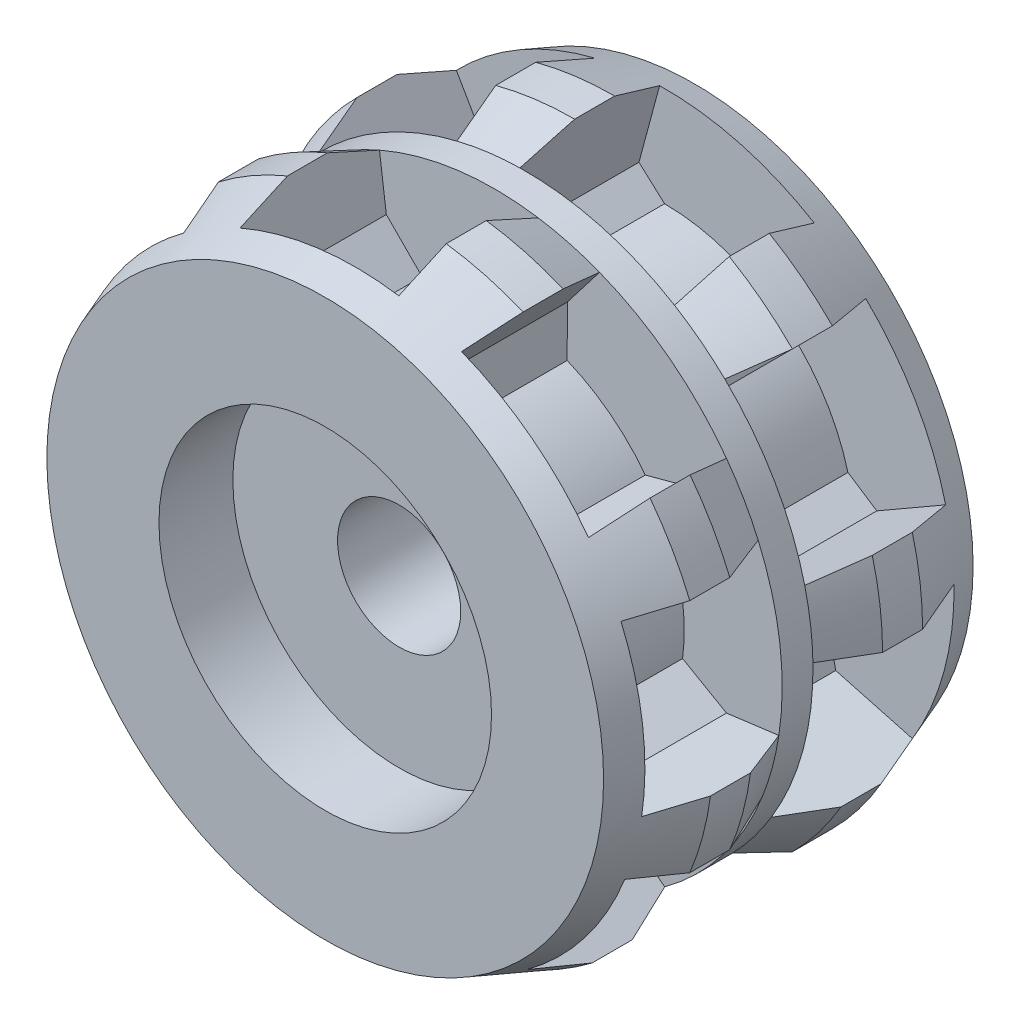
SolidWorks part; units mm, degrees
material "PTFE (general)"
ref_plane "Front Plane" through (0, 0, 0) normal (0, 0, 1) x (1, 0, 0)
ref_plane "Top Plane" through (0, 0, 0) normal (0, 1, 0) x (1, 0, 0)
ref_plane "Right Plane" through (0, 0, 0) normal (1, 0, 0) x (0, 0, -1)
sketch "Sketch1" plane through (0, 0, 0) normal (0, 0, 1) x (1, 0, 0)
  circle A0 centre (-57.4245, 16.5155) radius 23.35
  dimension "D1" = 46.7
extrude "Extrude1" add sketch "Sketch1" along normal blind 2.5
sketch "Sketch2" plane through (0, 0, 2.5) normal (0, 0, 1) x (1, 0, 0)
  circle A0 centre (-57.4245, 16.5155) radius 5
  dimension "D1" = 10
extrude "Extrude2" cut sketch "Sketch2" against normal up to next
sketch "Sketch3" plane through (0, 0, 0) normal (0, 0, -1) x (-1, 0, 0)
  circle A0 centre (57.4245, 16.5155) radius 25
  circle A1 centre (57.4245, 16.5155) radius 5
  dimension "D1" = 10
  dimension "D2" = 50
extrude "Extrude3" add sketch "Sketch3" along normal blind 13.75
sketch "Sketch4" plane through (0, 0, 2.5) normal (0, 0, 1) x (1, 0, 0)
  circle A0 centre (-57.4245, 16.5155) radius 5
  circle A1 centre (-57.4245, 16.5155) radius 25
  dimension "D1" = 50
  dimension "D2" = 10
extrude "Extrude4" add sketch "Sketch4" along normal blind 13.75
chamfer "Chamfer1" distance 1.65 distance2 4 2 edges at (-82.4245, 16.5155, 0) (-32.4245, 16.5155, 2.5) first distance on face at (-82.4245, 16.5155, 0) first distance on face at (-32.4245, 16.5155, 2.5)
chamfer "Chamfer2" distance 6.5 distance2 2.4 2 edges at (-82.4245, 16.5155, -13.75) (-32.4245, 16.5155, 16.25) first distance on face at (-82.4245, 16.5155, -4) first distance on face at (-32.4245, 16.5155, 6.5)
sketch "Sketch5" plane through (0, 0, 0) normal (0, 0, 1) x (1, 0, 0)
  line L0 (-57.4245, 41.5155) -> (-57.4245, 31.9155) construction
  line L1 (-44.8716, 38.1355) -> (-49.692, 29.8334) construction
  line L2 (-57.4245, 41.5155) -> (-59.5045, 33.7906)
  line L3 (-59.5045, 33.7906) -> (-57.4245, 31.9155)
  line L4 (-49.692, 29.8334) -> (-46.9516, 30.4106)
  line L5 (-46.9516, 30.4106) -> (-44.8716, 38.1355)
  line L6 (-46.9516, 30.4106) -> (-59.5045, 33.7906) construction
  line L7 (-53.2281, 32.1006) -> (-57.4245, 16.5155) construction
  line L8 (-50.9245, 40.6557) -> (-53.2281, 32.1006) construction
  line L9 (-39.7469, 34.1932) -> (-46.68, 30.2016)
  line L10 (-40.1937, 18.9354) -> (-33.2606, 22.9269)
  line L11 (-42.5396, 20.4649) -> (-40.1937, 18.9354)
  line L12 (-46.68, 30.2016) -> (-46.5351, 27.4049)
  line L13 (-32.4245, 16.5155) -> (-40.1494, 18.5955)
  line L14 (-43.5294, 6.0426) -> (-35.8045, 3.9626)
  line L15 (-44.1066, 8.7829) -> (-43.5294, 6.0426)
  line L16 (-40.1494, 18.5955) -> (-42.0245, 16.5155)
  line L17 (-39.7469, -1.1622) -> (-43.7384, 5.7709)
  line L18 (-55.0047, -0.7153) -> (-51.0131, -7.6484)
  line L19 (-53.4751, 1.6305) -> (-55.0047, -0.7153)
  line L20 (-43.7384, 5.7709) -> (-46.5351, 5.626)
  line L21 (-57.4245, -8.4845) -> (-55.3445, -0.7596)
  line L22 (-67.8975, 2.6204) -> (-69.9775, -5.1045)
  line L23 (-65.1571, 3.1976) -> (-67.8975, 2.6204)
  line L24 (-55.3445, -0.7596) -> (-57.4245, 1.1155)
  line L25 (-75.1022, -1.1622) -> (-68.1691, 2.8293)
  line L26 (-74.6554, 14.0956) -> (-81.5884, 10.1041)
  line L27 (-72.3095, 12.5661) -> (-74.6554, 14.0956)
  line L28 (-68.1691, 2.8293) -> (-68.314, 5.626)
  line L29 (-82.4245, 16.5155) -> (-74.6997, 14.4355)
  line L30 (-71.3197, 26.9884) -> (-79.0445, 29.0684)
  line L31 (-70.7425, 24.2481) -> (-71.3197, 26.9884)
  line L32 (-74.6997, 14.4355) -> (-72.8245, 16.5155)
  line L33 (-75.1022, 34.1932) -> (-71.1107, 27.2601)
  line L34 (-59.8444, 33.7463) -> (-63.8359, 40.6794)
  line L35 (-61.374, 31.4004) -> (-59.8444, 33.7463)
  line L36 (-71.1107, 27.2601) -> (-68.314, 27.4049)
  arc A0 (-57.4245, 41.5155) -> (-44.8716, 38.1355) centre (-57.4245, 16.5155) cw
  circle A1 centre (-57.4245, 16.5155) radius 25 construction
  arc A2 (-57.4245, 31.9155) -> (-49.692, 29.8334) centre (-57.4245, 16.5155) cw
  arc A3 (-39.7469, 34.1932) -> (-33.2606, 22.9269) centre (-57.4245, 16.5155) cw
  arc A4 (-46.5351, 27.4049) -> (-42.5396, 20.4649) centre (-57.4245, 16.5155) cw
  arc A5 (-32.4245, 16.5155) -> (-35.8045, 3.9626) centre (-57.4245, 16.5155) cw
  arc A6 (-42.0245, 16.5155) -> (-44.1066, 8.7829) centre (-57.4245, 16.5155) cw
  arc A7 (-39.7469, -1.1622) -> (-51.0131, -7.6484) centre (-57.4245, 16.5155) cw
  arc A8 (-46.5351, 5.626) -> (-53.4751, 1.6305) centre (-57.4245, 16.5155) cw
  arc A9 (-57.4245, -8.4845) -> (-69.9775, -5.1045) centre (-57.4245, 16.5155) cw
  arc A10 (-57.4245, 1.1155) -> (-65.1571, 3.1976) centre (-57.4245, 16.5155) cw
  arc A11 (-75.1022, -1.1622) -> (-81.5884, 10.1041) centre (-57.4245, 16.5155) cw
  arc A12 (-68.314, 5.626) -> (-72.3095, 12.5661) centre (-57.4245, 16.5155) cw
  arc A13 (-82.4245, 16.5155) -> (-79.0445, 29.0684) centre (-57.4245, 16.5155) cw
  arc A14 (-72.8245, 16.5155) -> (-70.7425, 24.2481) centre (-57.4245, 16.5155) cw
  arc A15 (-75.1022, 34.1932) -> (-63.8359, 40.6794) centre (-57.4245, 16.5155) cw
  arc A16 (-68.314, 27.4049) -> (-61.374, 31.4004) centre (-57.4245, 16.5155) cw
  dimension "D1" = 13
  dimension "D2" = 9.6
  dimension "D3" = 8
extrude "Extrude5" cut sketch "Sketch5" against normal blind 11.3
ref_plane "Plane1" through (0, 0, 2.5) normal (0, 0, 1) x (1, 0, 0)
sketch "Sketch7" plane through (0, 0, 2.5) normal (0, 0, 1) x (1, 0, 0)
  line L0 (-47.8575, 39.6125) -> (-51.5312, 30.7432) construction
  line L1 (-37.5536, 31.686) -> (-45.184, 25.8605) construction
  line L2 (-57.4245, 16.5155) -> (-47.8575, 39.6125) construction
  line L3 (-57.4245, 16.5155) -> (-57.4245, 41.5155) construction
  line L4 (-47.8575, 39.6125) -> (-51.5158, 34.8568)
  line L5 (-51.5158, 34.8568) -> (-51.5312, 30.7432)
  line L6 (-45.184, 25.8605) -> (-41.2119, 26.9303)
  line L7 (-41.2119, 26.9303) -> (-37.5536, 31.686)
  line L8 (-51.5158, 34.8568) -> (-41.2119, 26.9303) construction
  line L9 (-46.3639, 30.8936) -> (-42.1813, 36.3307) construction
  line L10 (-46.3639, 30.8936) -> (-57.4245, 16.5155) construction
  line L11 (-34.3276, 26.0826) -> (-40.2772, 25.3067)
  line L12 (-40.2772, 25.3067) -> (-43.1968, 22.4088)
  line L13 (-42.1613, 14.4681) -> (-38.5961, 12.4158)
  line L14 (-38.5961, 12.4158) -> (-32.6465, 13.1917)
  line L15 (-34.3276, 6.9484) -> (-39.0832, 10.6068)
  line L16 (-39.0832, 10.6068) -> (-43.1968, 10.6222)
  line L17 (-48.0795, 4.275) -> (-47.0097, 0.3029)
  line L18 (-47.0097, 0.3029) -> (-42.2541, -3.3555)
  line L19 (-47.8575, -6.5815) -> (-48.6333, -0.6319)
  line L20 (-48.6333, -0.6319) -> (-51.5312, 2.2877)
  line L21 (-59.472, 1.2522) -> (-61.5242, -2.313)
  line L22 (-61.5242, -2.313) -> (-60.7483, -8.2626)
  line L23 (-66.9916, -6.5815) -> (-63.3332, -1.8258)
  line L24 (-63.3332, -1.8258) -> (-63.3179, 2.2877)
  line L25 (-69.6651, 7.1705) -> (-73.6372, 6.1007)
  line L26 (-73.6372, 6.1007) -> (-77.2955, 1.345)
  line L27 (-80.5215, 6.9484) -> (-74.5719, 7.7243)
  line L28 (-74.5719, 7.7243) -> (-71.6523, 10.6222)
  line L29 (-72.6878, 18.5629) -> (-76.253, 20.6151)
  line L30 (-76.253, 20.6151) -> (-82.2026, 19.8393)
  line L31 (-80.5215, 26.0826) -> (-75.7659, 22.4242)
  line L32 (-75.7659, 22.4242) -> (-71.6523, 22.4088)
  line L33 (-66.7696, 28.756) -> (-67.8394, 32.7281)
  line L34 (-67.8394, 32.7281) -> (-72.595, 36.3865)
  line L35 (-66.9916, 39.6125) -> (-66.2157, 33.6629)
  line L36 (-66.2157, 33.6629) -> (-63.3179, 30.7432)
  line L37 (-55.3771, 31.7788) -> (-53.3249, 35.3439)
  line L38 (-53.3249, 35.3439) -> (-54.1008, 41.2936)
  arc A0 (-47.8575, 39.6125) -> (-37.5536, 31.686) centre (-57.4245, 16.5155) cw
  arc A1 (-51.5312, 30.7432) -> (-45.184, 25.8605) centre (-57.4245, 16.5155) cw
  circle A3 centre (-57.4245, 16.5155) radius 25 construction
  arc A4 (-34.3276, 26.0826) -> (-32.6465, 13.1917) centre (-57.4245, 16.5155) cw
  arc A5 (-43.1968, 22.4088) -> (-42.1613, 14.4681) centre (-57.4245, 16.5155) cw
  arc A6 (-34.3276, 6.9484) -> (-42.2541, -3.3555) centre (-57.4245, 16.5155) cw
  arc A7 (-43.1968, 10.6222) -> (-48.0795, 4.275) centre (-57.4245, 16.5155) cw
  arc A8 (-47.8575, -6.5815) -> (-60.7483, -8.2626) centre (-57.4245, 16.5155) cw
  arc A9 (-51.5312, 2.2877) -> (-59.472, 1.2522) centre (-57.4245, 16.5155) cw
  arc A10 (-66.9916, -6.5815) -> (-77.2955, 1.345) centre (-57.4245, 16.5155) cw
  arc A11 (-63.3179, 2.2877) -> (-69.6651, 7.1705) centre (-57.4245, 16.5155) cw
  arc A12 (-80.5215, 6.9484) -> (-82.2026, 19.8393) centre (-57.4245, 16.5155) cw
  arc A13 (-71.6523, 10.6222) -> (-72.6878, 18.5629) centre (-57.4245, 16.5155) cw
  arc A14 (-80.5215, 26.0826) -> (-72.595, 36.3865) centre (-57.4245, 16.5155) cw
  arc A15 (-71.6523, 22.4088) -> (-66.7696, 28.756) centre (-57.4245, 16.5155) cw
  arc A16 (-66.9916, 39.6125) -> (-54.1008, 41.2936) centre (-57.4245, 16.5155) cw
  arc A17 (-63.3179, 30.7432) -> (-55.3771, 31.7788) centre (-57.4245, 16.5155) cw
  dimension "D1" = 13
  dimension "D2" = 9.6
  dimension "D3" = 22.5
  dimension "D4" = 6
extrude "Extrude6" cut sketch "Sketch7" along normal blind 11.3
ref_plane "Plane2" through (0, 0, -5.5) normal (0, 0, -1) x (-1, 0, 0)
sketch "Sketch9" plane through (0, 0, 16.25) normal (0, 0, 1) x (1, 0, 0)
  circle A0 centre (-57.4245, 16.5155) radius 13.5
  circle A1 centre (-57.4245, 16.5155) radius 9.75
  dimension "D1" = 19.5
  dimension "D2" = 27
extrude "Extrude7" cut sketch "Sketch9" against normal blind 6
sketch "Sketch10" plane through (0, 0, -13.75) normal (0, 0, -1) x (-1, 0, 0)
  circle A0 centre (57.4245, 16.5155) radius 9.75
  circle A1 centre (57.4245, 16.5155) radius 13.5
  dimension "D1" = 19.5
  dimension "D2" = 27
extrude "Extrude8" cut sketch "Sketch10" against normal blind 6
sketch "Sketch11" plane through (0, 0, 16.25) normal (0, 0, 1) x (1, 0, 0)
  circle A0 centre (-57.4245, 16.5155) radius 9.75
  dimension "D1" = 19.5
extrude "Extrude9" cut sketch "Sketch11" against normal blind 6
